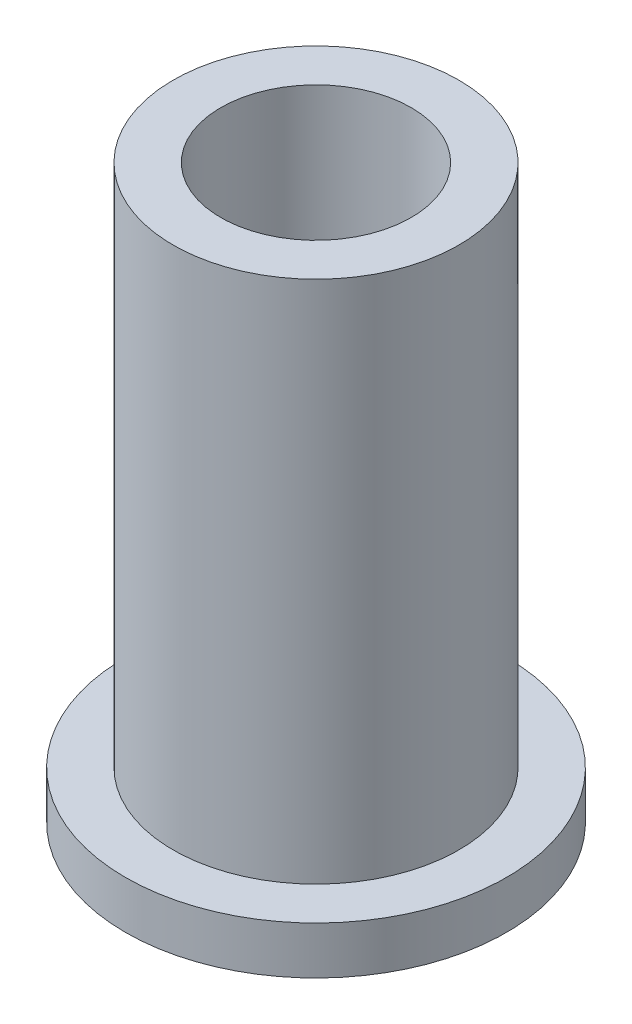
SolidWorks part; units mm, degrees
material "Commercial Bronze, UNS C22000 (90-10 Bronze)"
ref_plane "Front Plane" through (0, 0, 0) normal (0, 0, 1) x (1, 0, 0)
ref_plane "Top Plane" through (0, 0, 0) normal (0, 1, 0) x (1, 0, 0)
ref_plane "Right Plane" through (0, 0, 0) normal (1, 0, 0) x (0, 0, -1)
sketch "Sketch1" plane through (0, 0, 0) normal (0, 1, 0) x (1, 0, 0)
  circle A0 centre (0, 0) radius 3.175
  circle A1 centre (0, 0) radius 4.7625
  dimension "D1" = 6.35
  dimension "D2" = 9.525
extrude "Boss-Extrude1" add sketch "Sketch1" along normal blind 19.05
sketch "Sketch2" plane through (0, 0, 0) normal (0, -1, 0) x (1, 0, 0)
  circle A0 centre (0, 0) radius 4.7625 construction
  circle A1 centre (0, 0) radius 4.7625
  circle A2 centre (0, 0) radius 6.35
  dimension "D1" = 12.7
extrude "Boss-Extrude2" add sketch "Sketch2" against normal blind 1.5875
